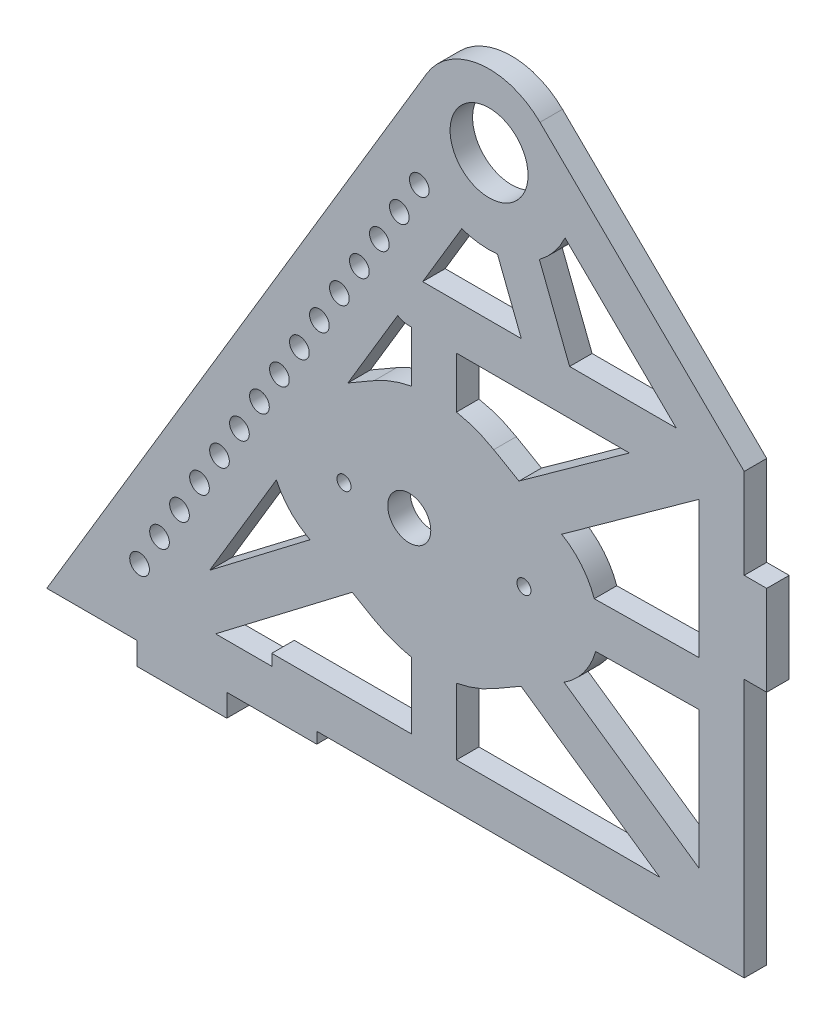
SolidWorks part; units mm, degrees
ref_plane "Front Plane" through (0, 0, 0) normal (0, 0, 1) x (1, 0, 0)
ref_plane "Top Plane" through (0, 0, 0) normal (0, 1, 0) x (1, 0, 0)
ref_plane "Right Plane" through (0, 0, 0) normal (1, 0, 0) x (0, 0, -1)
sketch "Sketch2" plane through (0, 0, 0) normal (0, 0, 1) x (1, 0, 0)
  line L1 (50.8, 6.35) -> (76.2, 6.35)
  line L2 (0, 6.35) -> (107.2144, 185.7594)
  line L4 (76.2, 6.35) -> (76.2, 9.525)
  line L6 (0, 6.35) -> (0, 0)
  line L7 (0, 0) -> (25.4, 0) construction
  line L8 (25.4, 6.35) -> (25.4, 0)
  line L13 (76.2, 9.525) -> (83.9864, 9.525)
  line L17 (0, -29.7981) -> (203.2, -29.7981) construction
  line L20 (196.85, 9.525) -> (196.85, 82.55)
  line L22 (196.85, 133.35) -> (139.2046, 189.8844)
  line L23 (196.85, 107.95) -> (196.85, 133.35)
  line L24 (196.85, 107.95) -> (203.2, 107.95)
  line L26 (196.85, 82.55) -> (203.2, 82.55)
  line L27 (203.2, 107.95) -> (203.2, 82.55)
  line L28 (83.9864, 9.525) -> (196.85, 9.525)
  line L29 (0, 6.35) -> (25.4, 6.35)
  line L30 (25.4, 0) -> (50.8, 0)
  line L31 (50.8, 0) -> (50.8, 6.35)
  arc A0 (139.2046, 189.8844) -> (107.2144, 185.7594) centre (124.8331, 175.2305) ccw
  circle A1 centre (124.8331, 175.2305) radius 11 construction
  circle A2 centre (124.8331, 175.2305) radius 4 construction
  circle A3 centre (124.8331, 175.2305) radius 11
  dimension "D3" = 22
  dimension "D4" = 9.525
  dimension "D5" = 8
  dimension "D6" = 22
  dimension "D1" = 168.8805
  dimension "D2" = 124.8331
  dimension "D7" = 6.35
  dimension "D8" = 25.4
  dimension "D9" = 3.175
  dimension "D10" = 6.35
  dimension "D11" = 73.025
  dimension "D12" = 203.2
  dimension "D13" = 76.2
  dimension "D14" = 6.35
  dimension "D15" = 25.4
  dimension "D16" = 6.35
  dimension "D17" = 25.4
  dimension "D18" = 25.4
extrude "Boss-Extrude1" add sketch "Sketch2" along normal blind 6.35 contours L22 A0 L2 L29 L8 L30 L31 L1 L4 L13 L28 L20 L26 L27 L24 L23 A3 region at (118.2801, 80.4306, 0)
sketch "Sketch4" [suppressed] plane through (0, 0, 6.35) normal (0, 0, 1) x (1, 0, 0)
  line L0 (1673.3123, 156.2334) -> (1577.5737, -3.9728)
  line L1 (1691.5051, 171.4226) -> (1750.822, 113.2489)
  line L2 (1684.7881, 175.4367) -> (1577.5737, -3.9728) construction
  line L3 (1590.9538, 18.4171) -> (1750.822, 18.4171)
  line L4 (1686.3016, 73.3904) -> (1617.2071, 143.6449) construction
  line L7 (1681.7742, 68.9378) -> (1612.6797, 139.1923)
  line L10 (1690.8289, 77.843) -> (1621.7344, 148.0975)
  line L13 (1566.672, 2.5421) -> (1566.672, -3.8079)
  line L14 (1566.672, -3.8079) -> (1592.072, -3.8079)
  line L15 (1592.072, -3.8079) -> (1592.072, 2.5421)
  line L16 (1592.072, 2.5421) -> (1642.872, 2.5421)
  line L17 (1642.872, 2.5421) -> (1642.872, 5.7171)
  line L18 (1642.872, 5.7171) -> (1763.522, 5.7171)
  line L24 (1763.522, 5.7171) -> (1763.522, 78.7421)
  line L25 (1673.8864, 181.9515) -> (1566.672, 2.5421)
  line L26 (1566.672, 2.5421) -> (1566.672, -3.8079)
  line L27 (1566.672, -3.8079) -> (1592.072, -3.8079)
  line L28 (1592.072, -3.8079) -> (1592.072, 2.5421)
  line L29 (1592.072, 2.5421) -> (1642.872, 2.5421)
  line L30 (1642.872, 2.5421) -> (1642.872, 5.7171)
  line L31 (1642.872, 5.7171) -> (1763.522, 5.7171)
  line L38 (1673.8864, 181.9515) -> (1566.672, 2.5421)
  line L39 (1686.3016, 73.3904) -> (1776.688, 147.3217) construction
  line L42 (1682.2812, 78.3056) -> (1772.6676, 152.2368)
  line L45 (1690.3219, 68.4752) -> (1780.7084, 142.4065)
  line L46 (1686.3016, 73.3904) -> (1535.3984, -21.6576) construction
  line L47 (1750.822, 113.2489) -> (1750.822, 18.4171)
  line L48 (1689.6858, 68.0174) -> (1538.7827, -27.0307)
  line L49 (1682.9173, 78.7634) -> (1532.0142, -16.2846)
  line L50 (1686.3016, 73.3904) -> (1767.8024, 12.8123) construction
  line L51 (1690.0896, 78.4868) -> (1771.5905, 17.9087)
  line L52 (1682.5135, 68.294) -> (1764.0144, 7.7159)
  line L53 (1691.5051, 171.4226) -> (1681.8948, -9.6316) construction
  line L54 (1697.8462, 171.086) -> (1688.2358, -9.9682)
  line L55 (1685.1641, 171.7592) -> (1675.5537, -9.2951)
  line L60 (1763.522, 5.7171) -> (1763.522, 78.7421)
  line L61 (1763.522, 129.5421) -> (1705.8766, 186.0765)
  line L62 (1763.522, 129.5421) -> (1705.8766, 186.0765)
  line L68 (1763.522, 78.7421) -> (1769.872, 78.7421)
  line L69 (1763.522, 78.7421) -> (1769.872, 78.7421)
  line L70 (1769.872, 78.7421) -> (1769.872, 104.1421)
  line L71 (1769.872, 78.7421) -> (1769.872, 104.1421)
  line L72 (1769.872, 104.1421) -> (1763.522, 104.1421)
  line L73 (1769.872, 104.1421) -> (1763.522, 104.1421)
  line L74 (1763.522, 104.1421) -> (1763.522, 129.5421)
  line L75 (1763.522, 104.1421) -> (1763.522, 129.5421)
  arc A1 (1705.8766, 186.0765) -> (1673.8864, 181.9515) centre (1691.5051, 171.4226) ccw
  arc A2 (1705.8766, 186.0765) -> (1673.8864, 181.9515) centre (1691.5051, 171.4226) ccw
  circle A4 centre (1691.5051, 171.4226) radius 23.7
  circle A5 centre (1691.5051, 171.4226) radius 23.7
  arc A14 (1681.7742, 68.9378) -> (1690.8289, 77.843) centre (1686.3016, 73.3904) ccw
  arc A15 (1621.7344, 148.0975) -> (1612.6797, 139.1923) centre (1617.2071, 143.6449) ccw
  arc A16 (1682.2812, 78.3056) -> (1690.3219, 68.4752) centre (1686.3016, 73.3904) ccw
  arc A17 (1780.7084, 142.4065) -> (1772.6676, 152.2368) centre (1776.688, 147.3217) ccw
  arc A18 (1689.6858, 68.0174) -> (1682.9173, 78.7634) centre (1686.3016, 73.3904) ccw
  arc A19 (1532.0142, -16.2846) -> (1538.7827, -27.0307) centre (1535.3984, -21.6576) ccw
  arc A20 (1690.0896, 78.4868) -> (1682.5135, 68.294) centre (1686.3016, 73.3904) ccw
  arc A21 (1764.0144, 7.7159) -> (1771.5905, 17.9087) centre (1767.8024, 12.8123) ccw
  arc A22 (1697.8462, 171.086) -> (1685.1641, 171.7592) centre (1691.5051, 171.4226) ccw
  arc A23 (1675.5537, -9.2951) -> (1688.2358, -9.9682) centre (1681.8948, -9.6316) ccw
  point P15 (1651.7543, 108.5176)
  point P28 (1731.4948, 110.356)
  point P35 (1610.85, 25.8664)
  point P42 (1727.052, 43.1013)
  point P50 (1686.6999, 80.8955)
  dimension "D6" = 6.35
  dimension "D4" = 12.7
  dimension "D5" = 12.7
  dimension "D1" = 0
  dimension "D2" = 12.7
  dimension "D3" = 12.7
extrude "Cut-Extrude1" [suppressed] cut sketch "Sketch4" against normal through all contours L49 L7 L0 | A5 L0 L10 L55 | A5 L54 L42 L1 | L45 L51 L47 L1 | L52 L54 L3 | L55 L48 L3
fillet "Fillet1" [suppressed] radius 2.54
sketch "Sketch5" plane through (0, 0, 6.35) normal (0, 0, 1) x (1, 0, 0)
  arc A0 (107.7056, 77.303) -> (97.4063, 78.1479) centre (102.3066, 74.6857) ccw construction
  arc A1 (107.7056, 77.303) -> (97.4063, 78.1479) centre (102.3066, 74.6857) ccw construction
  arc A2 (107.7056, 77.303) -> (97.4063, 78.1479) centre (102.3066, 74.6857) cw construction
  arc A3 (107.7742, 77.3363) -> (97.344, 78.1919) centre (102.3066, 74.6857) cw
  arc A4 (107.7742, 77.3363) -> (97.344, 78.1919) centre (102.3066, 74.6857) ccw
  dimension "D1" = 0.0762
extrude "Cut-Extrude2" cut sketch "Sketch5" against normal through all both and the other way through all
sketch "Sketch6" plane through (0, 0, 0) normal (0, 0, -1) x (-1, 0, 0)
  circle A0 centre (-83.8831, 74.1134) radius 1.9844 construction
  circle A1 centre (-134.6831, 74.1134) radius 1.9844 construction
  circle A2 centre (-83.8831, 74.1134) radius 1.9844
  circle A3 centre (-134.6831, 74.1134) radius 1.9844
extrude "Cut-Extrude3" cut sketch "Sketch6" against normal through all both and the other way through all
sketch "Sketch8" plane through (0, 0, 0) normal (0, 0, -1) x (-1, 0, 0)
  line L0 (-101.5018, 151.4426) -> (-26.1791, 25.4) construction
  line L1 (0, 6.35) -> (-107.2144, 185.7594) construction
  line L2 (0, 6.35) -> (-25.4, 6.35) construction
  circle A0 centre (-105.1401, 157.5309) radius 2.7781
  circle A1 centre (-99.5, 148.093) radius 2.7781
  circle A2 centre (-93.86, 138.6551) radius 2.7781
  circle A3 centre (-88.2199, 129.2171) radius 2.7781
  circle A4 centre (-82.5798, 119.7792) radius 2.7781
  circle A5 centre (-76.9398, 110.3413) radius 2.7781
  circle A6 centre (-71.2997, 100.9034) radius 2.7781
  circle A7 centre (-65.6596, 91.4655) radius 2.7781
  circle A8 centre (-60.0196, 82.0275) radius 2.7781
  circle A9 centre (-54.3795, 72.5896) radius 2.7781
  circle A10 centre (-48.7394, 63.1517) radius 2.7781
  circle A11 centre (-43.0994, 53.7138) radius 2.7781
  circle A12 centre (-37.4593, 44.2758) radius 2.7781
  circle A13 centre (-31.8192, 34.8379) radius 2.7781
  circle A14 centre (-26.1791, 25.4) radius 2.7781
  circle A17 centre (-124.8331, 175.2305) radius 23.7
  circle A18 centre (-124.8331, 175.2305) radius 23.7 construction
  dimension "D2" = 5.5562
  dimension "D1" = 12.7
  dimension "D5" = 19.05
  dimension "D4" = 12.7
  dimension "D3" = 15
extrude "Cut-Extrude5" cut sketch "Sketch8" against normal through all
sketch "Sketch7" plane through (0, 0, 0) normal (0, 0, -1) x (-1, 0, 0)
  line L0 (-109.2831, 74.1134) -> (-109.2831, 22.225) construction
  line L3 (-102.9331, 74.1134) -> (-102.9331, 22.225)
  line L4 (-138.8522, 66.8967) -> (-119.8078, 55.8949) construction
  line L5 (-119.8078, 92.3319) -> (-138.8522, 81.3301) construction
  line L6 (-79.7141, 81.3301) -> (-98.7585, 92.3319) construction
  line L7 (-98.7585, 55.8949) -> (-79.7141, 66.8967) construction
  line L8 (-145.205, 55.8998) -> (-126.1606, 44.898)
  line L9 (-92.4057, 44.898) -> (-73.3613, 55.8998)
  line L10 (-73.3613, 92.327) -> (-92.4057, 103.3288)
  line L11 (-126.1606, 103.3288) -> (-145.205, 92.327)
  line L14 (-115.6331, 74.1134) -> (-115.6331, 22.225)
  line L17 (-109.2831, 74.1134) -> (-37.1793, 19.05) construction
  line L20 (-105.4291, 79.1601) -> (-33.3253, 24.0967)
  line L23 (-113.1372, 69.0667) -> (-41.0334, 14.0033)
  line L26 (-109.2831, 74.1134) -> (-184.15, 22.225) construction
  line L29 (-105.666, 68.8943) -> (-180.5328, 17.006)
  line L32 (-112.9003, 79.3324) -> (-187.7672, 27.444)
  line L35 (-109.2831, 74.1134) -> (-184.15, 128.017) construction
  line L36 (-130.3121, 180.8172) -> (-184.15, 128.017)
  line L37 (-184.15, 128.017) -> (-184.15, 22.225)
  line L38 (-184.15, 22.225) -> (-63.5, 22.225)
  line L39 (-63.5, 22.225) -> (-63.5, 19.05)
  line L40 (-63.5, 19.05) -> (-22.3844, 19.05)
  line L41 (-22.3844, 19.05) -> (-118.1161, 179.2446)
  line L42 (-130.3121, 180.8172) -> (-184.15, 128.017)
  line L43 (-184.15, 128.017) -> (-184.15, 22.225)
  line L44 (-184.15, 22.225) -> (-63.5, 22.225)
  line L45 (-63.5, 22.225) -> (-63.5, 19.05)
  line L46 (-63.5, 19.05) -> (-22.3844, 19.05)
  line L50 (-112.9935, 68.9601) -> (-187.8603, 122.8637)
  line L54 (-37.1793, 19.05) -> (-117.1202, 152.8207)
  line L55 (0, 6.35) -> (-107.2144, 185.7594) construction
  line L56 (-105.5728, 79.2666) -> (-180.4397, 133.1702)
  line L57 (-109.2831, 74.1134) -> (-184.15, 75.121) construction
  line L58 (-109.3686, 67.764) -> (-184.2355, 68.7716)
  line L59 (-109.1977, 80.4628) -> (-184.0645, 81.4704)
  line L60 (-184.15, 128.017) -> (-102.2976, 128.017) construction
  line L61 (-184.15, 134.367) -> (-102.2976, 134.367)
  line L62 (-184.15, 121.667) -> (-102.2976, 121.667)
  line L63 (-124.8331, 175.2305) -> (-143.2238, 128.017) construction
  line L64 (-118.9162, 172.9258) -> (-137.3068, 125.7122)
  line L65 (-130.7501, 177.5353) -> (-149.1408, 130.3217)
  line L66 (-109.2831, 74.1134) -> (-109.2831, 121.667) construction
  line L67 (-115.6331, 74.1134) -> (-115.6331, 121.667)
  line L68 (-102.9331, 74.1134) -> (-102.9331, 121.667)
  circle A0 centre (-124.8331, 175.2305) radius 11
  circle A1 centre (-124.8331, 175.2305) radius 23.7
  arc A2 (-118.1161, 179.2446) -> (-130.3121, 180.8172) centre (-124.8331, 175.2305) ccw
  arc A4 (-138.8522, 81.3301) -> (-138.8522, 66.8967) centre (-134.6831, 74.1134) ccw construction
  arc A6 (-79.7141, 66.8967) -> (-79.7141, 81.3301) centre (-83.8831, 74.1134) ccw construction
  arc A8 (-119.8078, 92.3319) -> (-98.7585, 92.3319) centre (-109.2831, 74.1134) cw construction
  arc A9 (-119.8078, 55.8949) -> (-98.7585, 55.8949) centre (-109.2831, 74.1134) ccw construction
  arc A10 (-126.1606, 44.898) -> (-92.4057, 44.898) centre (-109.2831, 74.1134) ccw
  arc A11 (-73.3613, 55.8998) -> (-73.3613, 92.327) centre (-83.8831, 74.1134) ccw
  arc A12 (-126.1606, 103.3288) -> (-92.4057, 103.3288) centre (-109.2831, 74.1134) cw
  arc A13 (-145.205, 92.327) -> (-145.205, 55.8998) centre (-134.6831, 74.1134) ccw
  arc A36 (-102.9331, 74.1134) -> (-115.6331, 74.1134) centre (-109.2831, 74.1134) ccw
  arc A37 (-115.6331, 22.225) -> (-102.9331, 22.225) centre (-109.2831, 22.225) ccw
  arc A38 (-105.4291, 79.1601) -> (-113.1372, 69.0667) centre (-109.2831, 74.1134) ccw
  arc A39 (-41.0334, 14.0033) -> (-33.3253, 24.0967) centre (-37.1793, 19.05) ccw
  arc A40 (-105.666, 68.8943) -> (-112.9003, 79.3324) centre (-109.2831, 74.1134) ccw
  arc A41 (-187.7672, 27.444) -> (-180.5328, 17.006) centre (-184.15, 22.225) ccw
  arc A42 (-112.9935, 68.9601) -> (-105.5728, 79.2666) centre (-109.2831, 74.1134) ccw
  arc A43 (-180.4397, 133.1702) -> (-187.8603, 122.8637) centre (-184.15, 128.017) ccw
  arc A44 (-109.3686, 67.764) -> (-109.1977, 80.4628) centre (-109.2831, 74.1134) ccw
  arc A45 (-184.0645, 81.4704) -> (-184.2355, 68.7716) centre (-184.15, 75.121) ccw
  arc A46 (-184.15, 134.367) -> (-184.15, 121.667) centre (-184.15, 128.017) ccw
  arc A47 (-102.2976, 121.667) -> (-102.2976, 134.367) centre (-102.2976, 128.017) ccw
  arc A48 (-118.9162, 172.9258) -> (-130.7501, 177.5353) centre (-124.8331, 175.2305) ccw
  arc A49 (-149.1408, 130.3217) -> (-137.3068, 125.7122) centre (-143.2238, 128.017) ccw
  arc A50 (-115.6331, 74.1134) -> (-102.9331, 74.1134) centre (-109.2831, 74.1134) ccw
  arc A51 (-102.9331, 121.667) -> (-115.6331, 121.667) centre (-109.2831, 121.667) ccw
  point P28 (-109.2831, 48.1692)
  point P35 (-73.2312, 46.5817)
  point P41 (-146.7166, 48.1692)
  point P49 (-146.7166, 101.0652)
  point P60 (-146.7166, 74.6172)
  point P67 (-143.2238, 128.017)
  point P72 (-134.0285, 151.6237)
  point P80 (-109.2831, 97.8902)
  dimension "D3" = 22
  dimension "D5" = 6.35
  dimension "D6" = 25.4
  dimension "D1" = 12.7
  dimension "D2" = 12.7
  dimension "D4" = 12.7
extrude "Cut-Extrude4" cut sketch "Sketch7" against normal blind 50.8 contours A1 L42 L61 L65 | A1 L64 L61 L54 | L11 A12 L67 L62 L56 | A45 L59 A13 L50 L43 | A13 L58 L43 L32 | A10 L8 L29 L44 L14 | A10 L3 L44 L45 L46 L23 L9 | A11 L9 L20 L54 | A47 L62 L68 A12 L10 L54 region at (82.03, 31.433, 0) region at (61.3449, 51.0797, 0) region at (96.6831, 111.2016, 0) region at (137.5592, 32.2407, 0) region at (134.9118, 113.4356, 0) region at (169.8713, 54.0134, 0) region at (120.7556, 141.8155, 0) region at (169.6774, 95.7143, 0) region at (154.6845, 145.9667, 0)
